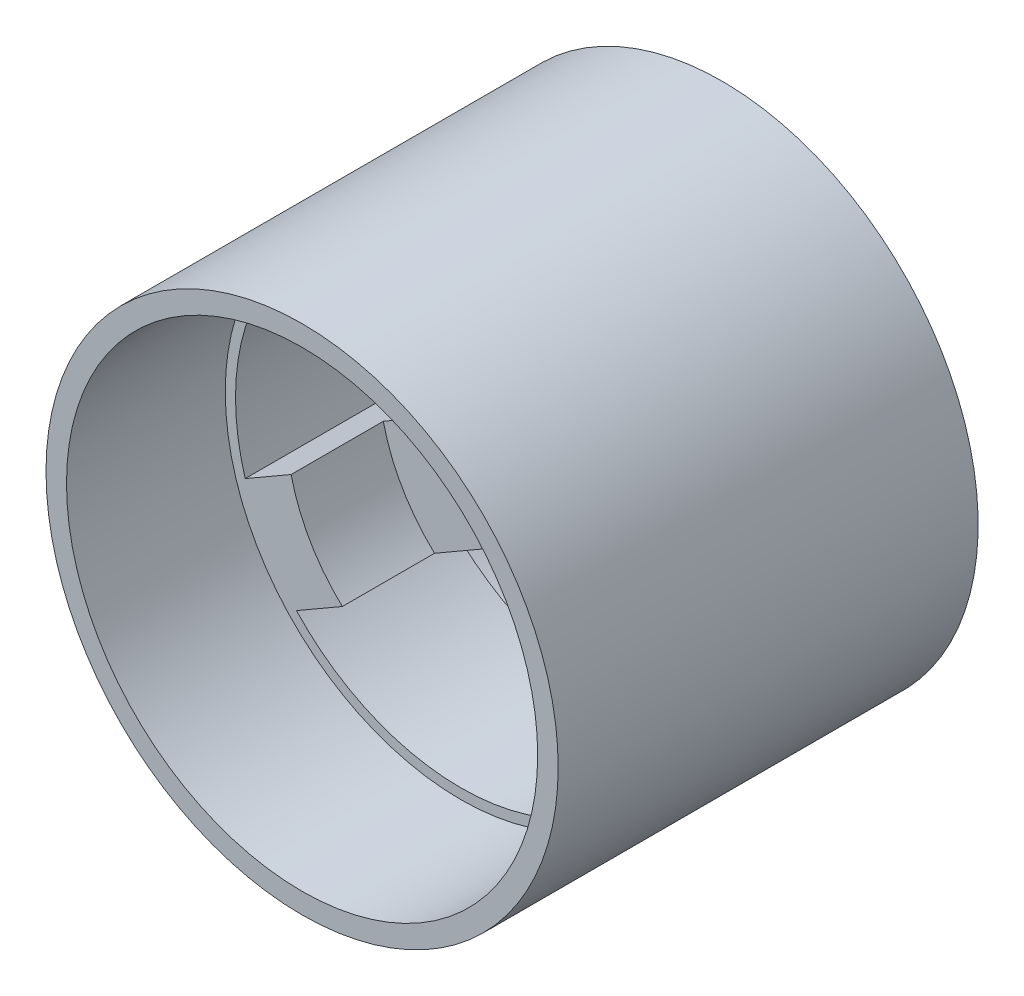
SolidWorks part; units mm, degrees
ref_plane "前视基准面" through (0, 0, 0) normal (0, 0, 1) x (1, 0, 0)
ref_plane "上视基准面" through (0, 0, 0) normal (0, 1, 0) x (1, 0, 0)
ref_plane "右视基准面" through (0, 0, 0) normal (1, 0, 0) x (0, 0, -1)
sketch "草图1" plane through (0, 0, 0) normal (0, 0, 1) x (1, 0, 0)
  circle A0 centre (0, 0) radius 22
  circle A1 centre (0, 0) radius 17
extrude "凸台-拉伸1" add sketch "草图1" along normal blind 9
sketch "草图2" plane through (0, 0, 0) normal (0, 0, -1) x (-1, 0, 0)
  circle A0 centre (0, 0) radius 22
extrude "凸台-拉伸2" add sketch "草图2" along normal blind 3
sketch "草图3" plane through (0, 0, -3) normal (0, 0, -1) x (-1, 0, 0)
  circle A1 centre (0, 10) radius 1
  circle A2 centre (8.6603, -5) radius 1
  circle A3 centre (-8.6603, -5) radius 1
  point P12 (0, 0)
  dimension "D1" = 3
extrude "切除-拉伸1" cut sketch "草图3" against normal blind 3
sketch "草图4" plane through (0, 0, -3) normal (0, 0, -1) x (-1, 0, 0)
  line L1 (24.7877, -8.5377) -> (5, 2.8868)
  line L2 (5, 15) -> (5, 2.8868)
  line L3 (-6.1603, -9.3301) -> (0, -5.7735)
  line L4 (19.7877, -17.1979) -> (0, -5.7735)
  line L5 (-5, 10) -> (-5, 2.8868)
  line L9 (-5, 2.8868) -> (-28.9027, -10.9135)
  line L16 (-6.1603, -9.3301) -> (-23.9027, -19.5738)
  line L19 (-5, 10) -> (-5, 31.0066)
  line L21 (5, 31.0066) -> (5, 15)
  line L22 (5, 31.0066) -> (28.5963, 19.5438)
  line L23 (28.5963, 19.5438) -> (24.7877, -8.5377)
  line L24 (19.7877, -17.1979) -> (-4.0351, -32.4361)
  line L25 (-4.0351, -32.4361) -> (-23.9027, -19.5738)
  line L26 (-28.9027, -10.9135) -> (-27.6381, 27.1706)
  line L27 (-27.6381, 27.1706) -> (-5, 31.0066)
extrude "切除-拉伸2" cut sketch "草图4" against normal blind 25
sketch "草图5" plane through (0, 0, -3) normal (0, 0, -1) x (-1, 0, 0)
  circle A0 centre (0, 0) radius 4
extrude "切除-拉伸3" cut sketch "草图5" against normal blind 10
fillet "圆角1" radius 10 1 edges at (-5, 2.8868, -1.5)
fillet "圆角2" radius 10 2 edges at (5, 2.8868, -1.5) (0, -5.7735, -1.5)
sketch "草图7" plane through (0, 0, -3) normal (0, 0, -1) x (-1, 0, 0)
  circle A0 centre (0, 0) radius 25
  circle A1 centre (0, 0) radius 22
extrude "凸台-拉伸3" add sketch "草图7" against normal blind 30
sketch "草图8" plane through (0, 0, -3) normal (0, 0, -1) x (-1, 0, 0)
  line L0 (-21.054, -6.382) -> (-15.7536, -3.3218)
  line L2 (16.054, -15.0423) -> (10.7536, -11.9821)
  line L3 (16.054, -15.0423) -> (5, -8.6603) construction
  line L4 (-16.054, -15.0423) -> (-10.7536, -11.9821)
  line L6 (21.054, -6.382) -> (15.7536, -3.3218)
  line L8 (5, 21.4243) -> (5, 15.3039)
  line L10 (-5, 21.4243) -> (-5, 15.3039)
  arc A0 (5, 15.3039) -> (-5, 15.3039) centre (0, 0) ccw
  arc A1 (16.054, -15.0423) -> (21.054, -6.382) centre (0, 0) ccw
  arc A2 (5, 21.4243) -> (-5, 21.4243) centre (0, 0) ccw
  arc A3 (-21.054, -6.382) -> (-16.054, -15.0423) centre (0, 0) ccw
  arc A4 (-15.7536, -3.3218) -> (-10.7536, -11.9821) centre (0, 0) ccw
  arc A5 (10.7536, -11.9821) -> (15.7536, -3.3218) centre (0, 0) ccw
extrude "凸台-拉伸4" add sketch "草图8" along normal blind 4
sketch "草图9" plane through (0, 0, -7) normal (0, 0, -1) x (-1, 0, 0)
  circle A0 centre (0, 0) radius 38.6725
extrude "切除-拉伸4" cut sketch "草图9" against normal blind 1
sketch "草图10" plane through (0, 0, -3) normal (0, 0, -1) x (-1, 0, 0)
  circle A0 centre (0, 0) radius 22
  circle A1 centre (0, 0) radius 25
extrude "凸台-拉伸5" add sketch "草图10" along normal blind 13.5
sketch "草图11" plane through (0, 0, -16.5) normal (0, 0, -1) x (-1, 0, 0)
  circle A0 centre (0, 0) radius 23
extrude "切除-拉伸5" cut sketch "草图11" against normal blind 10.5
chamfer "倒角2" distance 1 angle 45 1 edges at (-23, 0, -16.5)
sketch "草图12" plane through (0, 0, 27) normal (0, 0, 1) x (1, 0, 0)
  circle A0 centre (0, 0) radius 23
extrude "切除-拉伸6" cut sketch "草图12" against normal blind 18
sketch "草图13" plane through (0, 0, 27) normal (0, 0, 1) x (1, 0, 0)
  circle A0 centre (0, 0) radius 39.8309
extrude "切除-拉伸7" cut sketch "草图13" against normal blind 2.5
